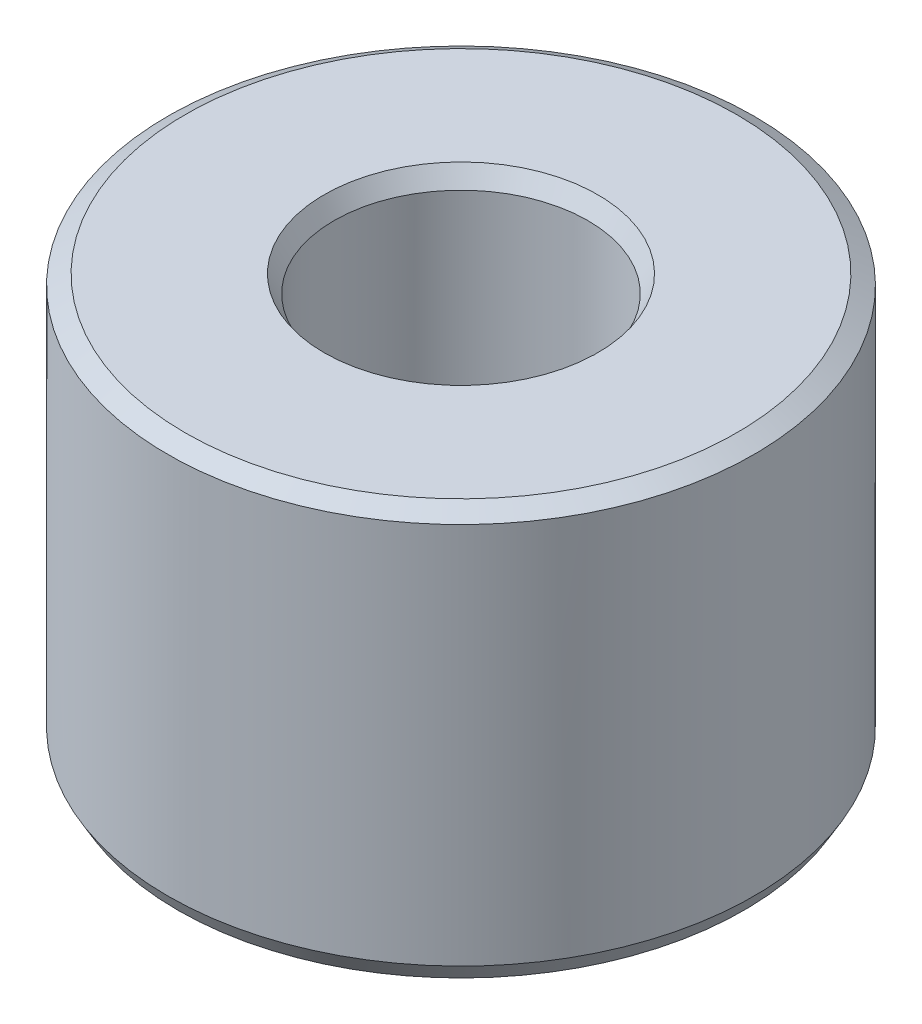
SolidWorks part; units mm, degrees
ref_plane "Front Plane" through (0, 0, 0) normal (0, 0, 1) x (1, 0, 0)
ref_plane "Top Plane" through (0, 0, 0) normal (0, 1, 0) x (1, 0, 0)
ref_plane "Right Plane" through (0, 0, 0) normal (1, 0, 0) x (0, 0, -1)
sketch "Sketch1" plane through (0, 0, 0) normal (0, 1, 0) x (1, 0, 0)
  circle A0 centre (0, 0) radius 55
  dimension "SLEEVE_OD" = 110
extrude "Boss-Extrude1" add sketch "Sketch1" along normal blind 76.9032
sketch "Sketch2" plane through (0, 0, 0) normal (0, 1, 0) x (1, 0, 0)
  circle A0 centre (0, 0) radius 23.8055
  dimension "BORE_D" = 47.611
extrude "Cut-Extrude1" cut sketch "Sketch2" along normal through all
chamfer "Chamfer1" distance 1.8809 angle 60 4 edges at (0, 76.9032, 23.8055) (0, 0, 23.8055) (0, 0, 55) (0, 76.9032, 55) first distance on face at (0, 76.9032, 23.8055) first distance on face at (0, 0, 23.8055) first distance on face at (0, 76.9032, 55)
